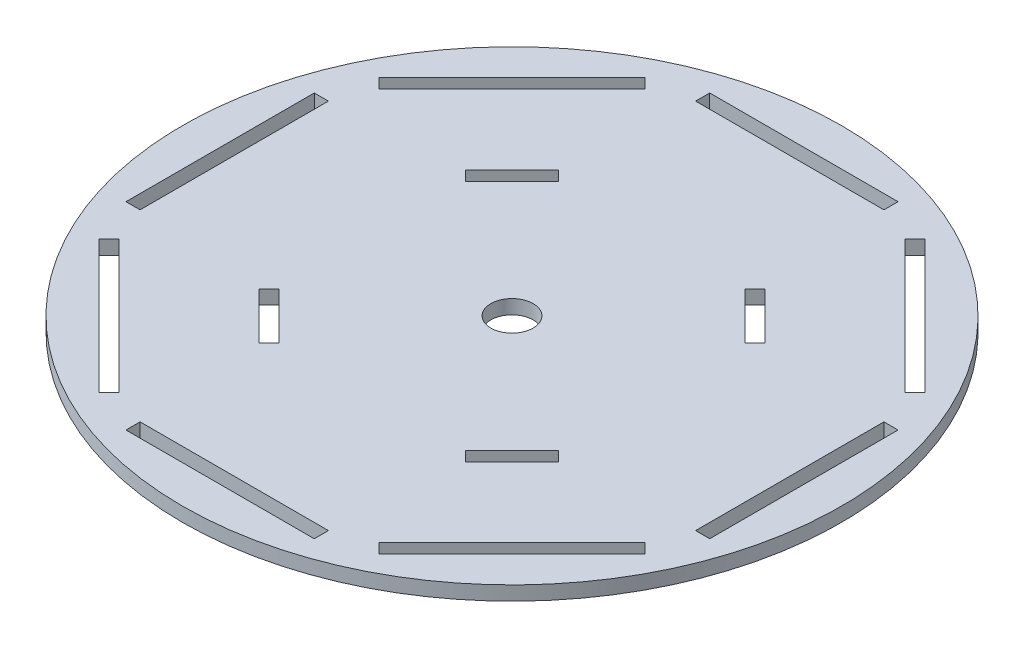
SolidWorks part; units mm, degrees
ref_plane "Alzado" through (0, 0, 0) normal (0, 0, 1) x (1, 0, 0)
ref_plane "Planta" through (0, 0, 0) normal (0, 1, 0) x (1, 0, 0)
ref_plane "Vista lateral" through (0, 0, 0) normal (1, 0, 0) x (0, 0, -1)
sketch "Croquis1" plane through (0, 0, 0) normal (0, 1, 0) x (1, 0, 0)
  line L0 (24.7487, 24.7487) -> (29.6985, 19.799)
  line L1 (29.6985, 19.799) -> (31.8198, 21.9203)
  line L2 (31.8198, 21.9203) -> (21.9203, 31.8198)
  line L3 (19.799, 29.6985) -> (21.9203, 31.8198)
  line L4 (24.7487, 24.7487) -> (19.799, 29.6985)
  line L5 (24.7487, -24.7487) -> (19.799, -29.6985)
  line L6 (19.799, -29.6985) -> (21.9203, -31.8198)
  line L7 (21.9203, -31.8198) -> (31.8198, -21.9203)
  line L8 (29.6985, -19.799) -> (31.8198, -21.9203)
  line L9 (24.7487, -24.7487) -> (29.6985, -19.799)
  line L10 (0, 0) -> (-24.7487, 24.7487) construction
  line L11 (-24.7487, 24.7487) -> (-19.799, 29.6985)
  line L12 (-19.799, 29.6985) -> (-21.9203, 31.8198)
  line L13 (-24.7487, -24.7487) -> (-29.6985, -19.799)
  line L14 (-29.6985, -19.799) -> (-31.8198, -21.9203)
  line L15 (-31.8198, -21.9203) -> (-21.9203, -31.8198)
  line L16 (-19.799, -29.6985) -> (-21.9203, -31.8198)
  line L17 (-24.7487, -24.7487) -> (-19.799, -29.6985)
  line L23 (-21.9203, 31.8198) -> (-31.8198, 21.9203)
  line L24 (-24.7487, 24.7487) -> (-29.6985, 19.799)
  line L25 (-29.6985, 19.799) -> (-31.8198, 21.9203)
  line L41 (0, 0) -> (0, 62) construction
  line L42 (0, 62) -> (20, 62)
  line L43 (20, 62) -> (20, 59)
  line L44 (20, 59) -> (-20, 59)
  line L45 (-20, 59) -> (-20, 62)
  line L46 (-20, 62) -> (0, 62)
  line L47 (55.8614, 27.5772) -> (27.5772, 55.8614)
  line L48 (27.5772, 55.8614) -> (29.6985, 57.9828)
  line L49 (29.6985, 57.9828) -> (43.8406, 43.8406)
  line L50 (43.8406, 43.8406) -> (57.9828, 29.6985)
  line L51 (57.9828, 29.6985) -> (55.8614, 27.5772)
  line L52 (59, -20) -> (59, 20)
  line L53 (59, 20) -> (62, 20)
  line L54 (62, 20) -> (62, 0)
  line L55 (62, 0) -> (62, -20)
  line L56 (62, -20) -> (59, -20)
  line L57 (27.5772, -55.8614) -> (55.8614, -27.5772)
  line L58 (55.8614, -27.5772) -> (57.9828, -29.6985)
  line L59 (57.9828, -29.6985) -> (43.8406, -43.8406)
  line L60 (43.8406, -43.8406) -> (29.6985, -57.9828)
  line L61 (29.6985, -57.9828) -> (27.5772, -55.8614)
  line L62 (-20, -59) -> (20, -59)
  line L63 (20, -59) -> (20, -62)
  line L64 (20, -62) -> (0, -62)
  line L65 (0, -62) -> (-20, -62)
  line L66 (-20, -62) -> (-20, -59)
  line L67 (-55.8614, -27.5772) -> (-27.5772, -55.8614)
  line L68 (-27.5772, -55.8614) -> (-29.6985, -57.9828)
  line L69 (-29.6985, -57.9828) -> (-43.8406, -43.8406)
  line L70 (-43.8406, -43.8406) -> (-57.9828, -29.6985)
  line L71 (-57.9828, -29.6985) -> (-55.8614, -27.5772)
  line L72 (-59, 20) -> (-59, -20)
  line L73 (-59, -20) -> (-62, -20)
  line L74 (-62, -20) -> (-62, 0)
  line L75 (-62, 0) -> (-62, 20)
  line L76 (-62, 20) -> (-59, 20)
  line L77 (-27.5772, 55.8614) -> (-55.8614, 27.5772)
  line L78 (-55.8614, 27.5772) -> (-57.9828, 29.6985)
  line L79 (-57.9828, 29.6985) -> (-43.8406, 43.8406)
  line L80 (-43.8406, 43.8406) -> (-29.6985, 57.9828)
  line L81 (-29.6985, 57.9828) -> (-27.5772, 55.8614)
  circle A0 centre (0, 0) radius 4.5
  circle A2 centre (0, 0) radius 70
  point P26 (0, 0)
  point P47 (0, 0)
  point P88 (0, 0)
  dimension "D2" = 7
  dimension "D3" = 140
  dimension "D4" = 35
  dimension "D5" = 4
  dimension "D9" = 7
  dimension "D10" = 3
  dimension "D15" = 20
  dimension "D16" = 3
  dimension "D17" = 40
  dimension "D18" = 8
extrude "Saliente-Extruir1" add sketch "Croquis1" along normal blind 3
